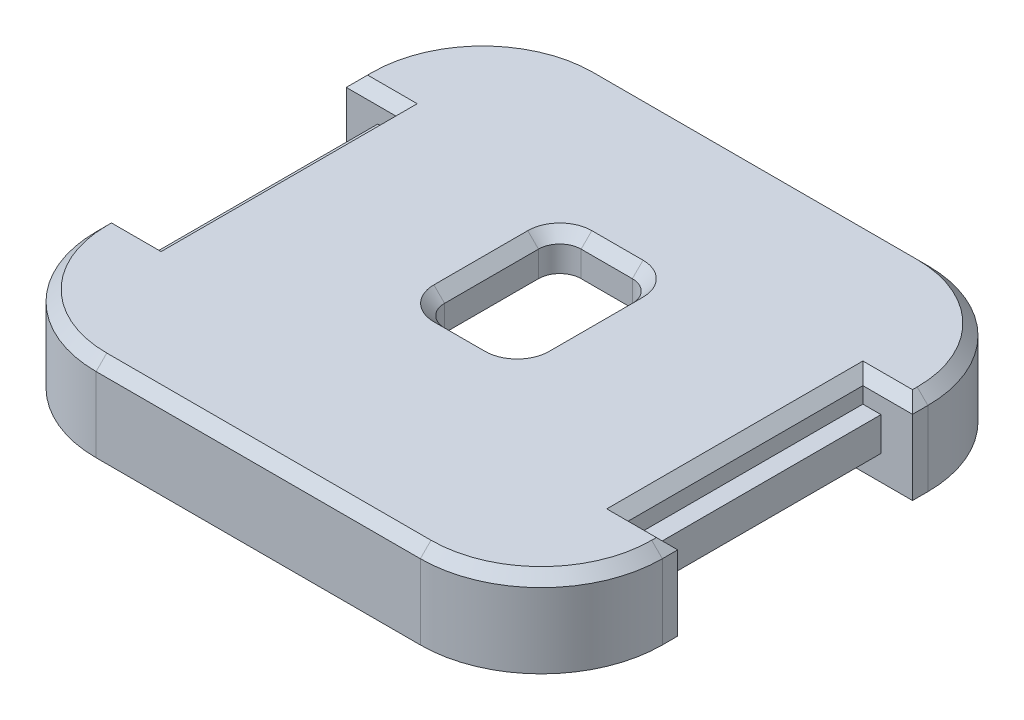
SolidWorks part; units mm, degrees
ref_plane "Front Plane" through (0, 0, 0) normal (0, 0, 1) x (1, 0, 0)
ref_plane "Top Plane" through (0, 0, 0) normal (0, 1, 0) x (1, 0, 0)
ref_plane "Right Plane" through (0, 0, 0) normal (1, 0, 0) x (0, 0, -1)
sketch "Sketch1" plane through (0, 1.7, 0) normal (0, 1, 0) x (1, 0, 0)
  line L4 (-13.265, 4.98) -> (-13.265, -7.46)
  line L5 (-7.595, -13.13) -> (7.595, -13.13)
  line L6 (13.265, -7.46) -> (13.265, 4.98)
  line L7 (7.595, 10.65) -> (-7.595, 10.65)
  line L8 (-13.265, 4.98) -> (-13.265, -7.46)
  line L9 (-7.595, -13.13) -> (7.595, -13.13)
  line L10 (13.265, -7.46) -> (13.265, 4.98)
  line L11 (7.595, 10.65) -> (-7.595, 10.65)
  arc A4 (-13.265, -7.46) -> (-7.595, -13.13) centre (-7.595, -7.46) ccw
  arc A5 (7.595, -13.13) -> (13.265, -7.46) centre (7.595, -7.46) ccw
  arc A6 (13.265, 4.98) -> (7.595, 10.65) centre (7.595, 4.98) ccw
  arc A7 (-7.595, 10.65) -> (-13.265, 4.98) centre (-7.595, 4.98) ccw
  arc A8 (-13.265, -7.46) -> (-7.595, -13.13) centre (-7.595, -7.46) ccw
  arc A9 (7.595, -13.13) -> (13.265, -7.46) centre (7.595, -7.46) ccw
  arc A10 (13.265, 4.98) -> (7.595, 10.65) centre (7.595, 4.98) ccw
  arc A11 (-7.595, 10.65) -> (-13.265, 4.98) centre (-7.595, 4.98) ccw
  dimension "D1" = 0
extrude "Boss-Extrude1" add sketch "Sketch1" against normal up to surface (4 mm away)
sketch "Sketch2" plane through (0, -6, 0) normal (0, -1, 0) x (-1, 0, 0)
  line L4 (7.595, 10.65) -> (-7.595, 10.65)
  line L5 (-13.265, 4.98) -> (-13.265, -7.46)
  line L6 (-7.595, -13.13) -> (7.595, -13.13)
  line L7 (13.265, -7.46) -> (13.265, 4.98)
  line L8 (7.595, 10.65) -> (-7.595, 10.65)
  line L9 (-13.265, 4.98) -> (-13.265, -7.46)
  line L10 (-7.595, -13.13) -> (7.595, -13.13)
  line L11 (13.265, -7.46) -> (13.265, 4.98)
  arc A4 (-7.595, 10.65) -> (-13.265, 4.98) centre (-7.595, 4.98) ccw
  arc A5 (-13.265, -7.46) -> (-7.595, -13.13) centre (-7.595, -7.46) ccw
  arc A6 (7.595, -13.13) -> (13.265, -7.46) centre (7.595, -7.46) ccw
  arc A7 (13.265, 4.98) -> (7.595, 10.65) centre (7.595, 4.98) ccw
  arc A8 (-7.595, 10.65) -> (-13.265, 4.98) centre (-7.595, 4.98) ccw
  arc A9 (-13.265, -7.46) -> (-7.595, -13.13) centre (-7.595, -7.46) ccw
  arc A10 (7.595, -13.13) -> (13.265, -7.46) centre (7.595, -7.46) ccw
  arc A11 (13.265, 4.98) -> (7.595, 10.65) centre (7.595, 4.98) ccw
  dimension "D1" = 0
sketch "Sketch5" plane through (0, 1.7, 0) normal (0, 1, 0) x (1, 0, 0)
  line L136 (-7.595, -10.48) -> (7.595, -10.48)
  line L137 (10.615, -7.46) -> (10.615, 4.98)
  line L138 (7.595, 8) -> (-7.595, 8)
  line L139 (-10.615, 4.98) -> (-10.615, -7.46)
  line L144 (-7.595, -10.48) -> (7.595, -10.48)
  line L145 (10.615, -7.46) -> (10.615, 4.98)
  line L146 (7.595, 8) -> (-7.595, 8)
  line L147 (-10.615, 4.98) -> (-10.615, -7.46)
  arc A136 (7.595, -10.48) -> (10.615, -7.46) centre (7.595, -7.46) ccw
  arc A137 (10.615, 4.98) -> (7.595, 8) centre (7.595, 4.98) ccw
  arc A138 (-7.595, 8) -> (-10.615, 4.98) centre (-7.595, 4.98) ccw
  arc A139 (-10.615, -7.46) -> (-7.595, -10.48) centre (-7.595, -7.46) ccw
  arc A144 (7.595, -10.48) -> (10.615, -7.46) centre (7.595, -7.46) ccw
  arc A145 (10.615, 4.98) -> (7.595, 8) centre (7.595, 4.98) ccw
  arc A146 (-7.595, 8) -> (-10.615, 4.98) centre (-7.595, 4.98) ccw
  arc A147 (-10.615, -7.46) -> (-7.595, -10.48) centre (-7.595, -7.46) ccw
  dimension "D1" = 0
extrude "Cut-Extrude1" cut sketch "Sketch5" against normal through all from vertex at -1.7
sketch "Sketch7" plane through (0, 1.7, 0) normal (0, 1, 0) x (1, 0, 0)
  line L1 (1.2, -2.2) -> (1.2, 2.2) construction
  line L2 (1.2, 2.2) -> (-1.2, 2.2) construction
  line L3 (-1.2, -2.2) -> (1.2, -2.2) construction
  line L4 (-1.2, 2.2) -> (-1.2, -2.2) construction
  line L6 (1.2, -2.2) -> (1.2, 2.2) construction
  line L7 (1.2, 2.2) -> (-1.2, 2.2) construction
  line L8 (-1.2, -2.2) -> (1.2, -2.2) construction
  line L9 (-1.2, 2.2) -> (-1.2, -2.2) construction
  line L10 (2.2, -2.2) -> (2.2, 2.2)
  line L11 (1.2, 3.2) -> (-1.2, 3.2)
  line L12 (-2.2, 2.2) -> (-2.2, -2.2)
  line L13 (-1.2, -3.2) -> (1.2, -3.2)
  line L14 (-2.2, 3.2) -> (-2.2, -3.2) construction
  line L15 (-2.2, -3.2) -> (2.2, -3.2) construction
  line L16 (2.2, -3.2) -> (2.2, 3.2) construction
  line L17 (2.2, 3.2) -> (-2.2, 3.2) construction
  arc A0 (-2.2, -2.2) -> (-1.2, -3.2) centre (-1.2, -2.2) ccw
  arc A1 (2.2, -2.2) -> (1.2, -3.2) centre (1.2, -2.2) cw
  arc A2 (2.2, 2.2) -> (1.2, 3.2) centre (1.2, 2.2) ccw
  arc A3 (-1.2, 3.2) -> (-2.2, 2.2) centre (-1.2, 2.2) ccw
  dimension "D2" = 1
  dimension "D1" = 1
extrude "Cut-Extrude2" cut sketch "Sketch7" against normal through all
sketch "Sketch11" plane through (0, 1.7, 0) normal (0, 1, 0) x (1, 0, 0)
  circle A0 centre (-7.615, 5.15) radius 2.1
  circle A1 centre (7.615, 5.15) radius 2.1
  dimension "D1" = 4.2
extrude "Cut-Extrude4" cut sketch "Sketch11" against normal through all
chamfer "Chamfer1" distance 1.25 angle 45 8 edges at (-10.615, 0, 1.24) (-9.7305, 0, 9.5955) (-9.7305, 0, -7.1155) (0, 0, 10.48) (0, 0, -8) (9.7305, 0, 9.5955) (9.7305, 0, -7.1155) (10.615, 0, 1.24)
sketch "Sketch12" plane through (0, 0, 1.24) normal (0, 0, 1) x (1, 0, 0)
  line L1 (11.79, -2.45) -> (13.415, -2.45)
  line L2 (13.415, -2.45) -> (13.415, 1.85)
  line L6 (11.79, -1.125) -> (10.615, -2.3)
  line L7 (10.615, -2.3) -> (11.79, -2.3)
  line L8 (11.79, -2.3) -> (11.79, -2.45)
  line L9 (11.79, 0.55) -> (11.79, -2.45) construction
  line L10 (11.79, -1.125) -> (11.79, 0.45)
  line L11 (11.79, 0.45) -> (10.94, 0.45)
  line L12 (11.94, 0.7) -> (11.94, -2.3)
  line L13 (11.44, 0.7) -> (11.94, 0.7)
  line L14 (11.44, 1.7) -> (11.44, 0.7)
  line L15 (13.265, 1.7) -> (11.44, 1.7)
  line L16 (13.265, -2.3) -> (13.265, 1.7)
  line L17 (11.94, -2.3) -> (13.265, -2.3)
  line L18 (11.94, 0.7) -> (11.94, -2.3) construction
  line L19 (11.44, 0.7) -> (11.94, 0.7) construction
  line L20 (11.44, 1.7) -> (11.44, 0.7) construction
  line L21 (13.265, 1.7) -> (11.44, 1.7) construction
  line L22 (13.265, -2.3) -> (13.265, 1.7) construction
  line L23 (11.94, -2.3) -> (13.265, -2.3) construction
  line L37 (13.415, 1.85) -> (10.94, 1.85)
  line L38 (10.94, 1.85) -> (10.94, 0.45)
  line L40 (11.29, 1.85) -> (11.29, 0.55) construction
  line L41 (11.29, 0.55) -> (11.79, 0.55) construction
  line L42 (13.415, 1.85) -> (11.29, 1.85) construction
  dimension "D3" = 45
  dimension "D4" = 0.5
  dimension "D5" = 0.25
  dimension "D6" = 0.15
  dimension "D1" = 0
  dimension "D2" = 0.15
extrude "Cut-Extrude5" cut sketch "Sketch12" against normal mid plane 11
mirror "Mirror1" about plane through (0, 0, 0) normal (1, 0, 0) of "Cut-Extrude5"
sketch "Sketch13" plane through (0, 1.7, 0) normal (0, 1, 0) x (1, 0, 0)
  circle A0 centre (7.615, 5.15) radius 2.1 construction
  circle A1 centre (-7.615, 5.15) radius 2.1 construction
  circle A2 centre (7.615, 5.15) radius 2.1
  circle A3 centre (-7.615, 5.15) radius 2.1
extrude "Boss-Extrude4" add sketch "Sketch13" against normal blind 0.5
chamfer "Chamfer3" distance 0.5 angle 45 24 edges at (0, 1.7, 3.2) (1.9071, 1.7, 2.9071) (2.2, 1.7, 0) (1.9071, 1.7, -2.9071) (0, 1.7, -3.2) (-1.9071, 1.7, -2.9071) (-2.2, 1.7, 0) (-1.9071, 1.7, 2.9071) (-13.265, 1.7, -4.62) (-11.6043, 1.7, -8.9893) (0, 1.7, -10.65) (11.6043, 1.7, -8.9893) (13.265, 1.7, -4.62) (12.1025, 1.7, -4.26) (10.94, 1.7, 1.24) (12.1025, 1.7, 6.74) (13.265, 1.7, 7.1) (11.6043, 1.7, 11.4693) (0, 1.7, 13.13) (-11.6043, 1.7, 11.4693) (-13.265, 1.7, 7.1) (-12.1025, 1.7, 6.74) (-10.94, 1.7, 1.24) (-12.1025, 1.7, -4.26)
